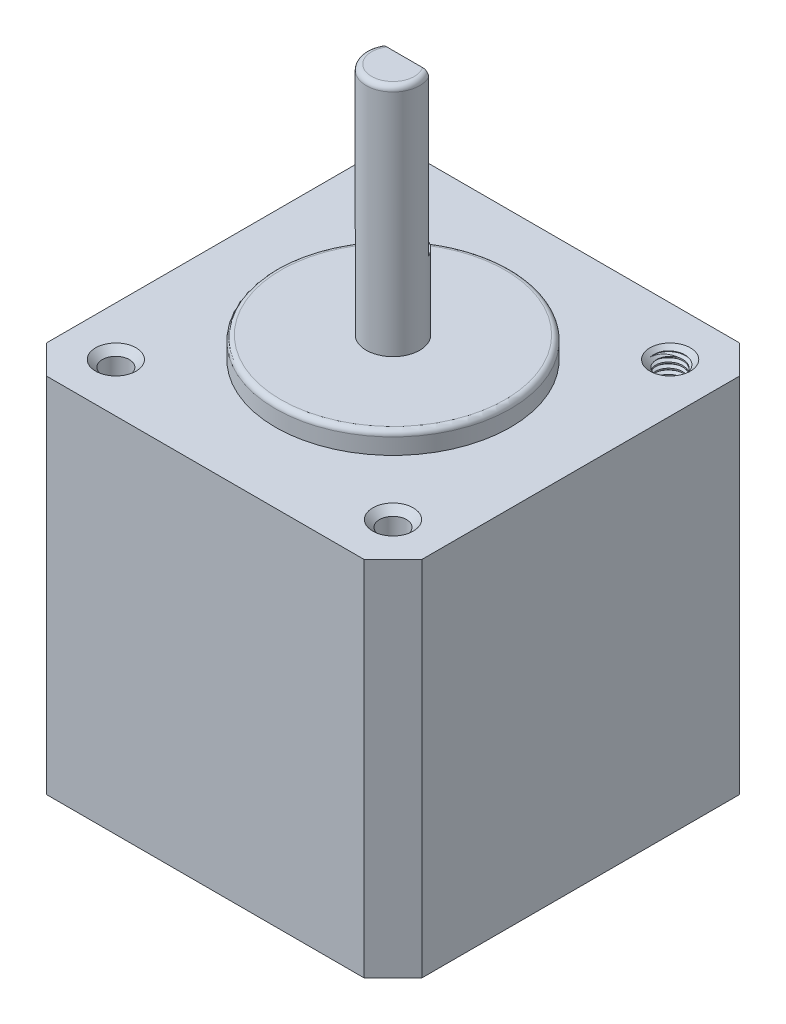
SolidWorks part; units mm, degrees
ref_plane "Front Plane" through (0, 0, 0) normal (0, 0, 1) x (1, 0, 0)
ref_plane "Top Plane" through (0, 0, 0) normal (0, 1, 0) x (1, 0, 0)
ref_plane "Right Plane" through (0, 0, 0) normal (1, 0, 0) x (0, 0, -1)
sketch "Sketch1" plane through (0, 0, 0) normal (0, 1, 0) x (1, 0, 0)
  line L1 (-17.6, -17.6) -> (17.6, -17.6)
  line L2 (-17.6, -17.6) -> (-17.6, 17.6)
  line L3 (-17.6, 17.6) -> (17.6, 17.6)
  line L4 (17.6, -17.6) -> (17.6, 17.6)
  line L5 (-17.6, -17.6) -> (17.6, 17.6) construction
  line L6 (-17.6, 17.6) -> (17.6, -17.6) construction
  point P0 (0, 0)
  dimension "D1" = 35.2
extrude "Boss-Extrude1" add sketch "Sketch1" along normal blind 34
hole_wizard "#39 (0.0995) Diameter Hole1" positions "Sketch2" profile "Sketch4" hole size "#39" standard "ANSI Inch"
sketch "Sketch2" plane through (0, 34, 0) normal (0, 1, 0) x (1, 0, 0)
  line L0 (-17.6, 17.6) -> (17.6, -17.6) construction
  line L3 (-13, -13) -> (13, -13) construction
  line L4 (-13, -13) -> (-13, 13) construction
  line L5 (-13, 13) -> (13, 13) construction
  line L6 (13, -13) -> (13, 13) construction
  line L7 (-13, -13) -> (13, 13) construction
  line L8 (-13, 13) -> (13, -13) construction
  line L9 (17.6, -17.6) -> (17.6, 17.6) construction
  point P8 (13, 13)
  point P63 (-13, -13)
  point P64 (-13, 13)
  point P65 (13, -13)
  dimension "D1" = 26
  dimension "D2" = 4.6
sketch "Sketch4" plane through (13, 34, 13) normal (1, 0, 0) x (0, 0, 1)
  line L0 (0, 0) -> (0, 5.2953)
  line L1 (0, 5.2953) -> (1.2636, 4.536)
  line L2 (1.2636, 4.536) -> (1.2636, 0.635)
  line L3 (1.2636, 0.635) -> (1.8986, 0)
  line L5 (1.8986, 0) -> (0, 0)
  line L6 (-1.2636, 0.635) -> (-1.8986, 0) construction
  line L10 (0, 5.2953) -> (-1.2637, 4.536) construction
  line L11 (0, -6.35) -> (0, 107.95) construction
  dimension "Hole Dia." = 2.5273
  dimension "Hole Depth" = 4.536
  dimension "Near C'Sink Dia." = 3.7973
  dimension "Near C'Sink Angle" = 90
  dimension "Drill Angle" = 118
thread "M3 threads" pitch 0.5 method cut profile "Thread Profile3" start angle 0, offset 0, length 4.5, pitch 0.5, diameter 2.5273
ref_plane "Plane3" through (-14.2636, 33.365, -13) normal (0, 0, 1) x (-1, 0, 0)
sketch "Thread Profile3" plane through (-14.2636, 33.365, -13) normal (0, 0, 1) x (-1, 0, 0)
  line L0 (0, 0) -> (0, 0.5) construction
  line L1 (0, 0) -> (0.2706, 0.1562)
  line L2 (0.2706, 0.1562) -> (0.2706, 0.2187)
  line L3 (0.2706, 0.2187) -> (0, 0.375)
  line L4 (0.2706, 0.1875) -> (0, 0.1875) construction
  line L11 (0, 0) -> (0, 0.375)
  point P2 (0, 0)
  dimension "Pitch" = 0.5
  dimension "Profile_Angle" = 60
  dimension "Profile_Land" = 0.0625
  dimension "Profile_Height" = 0.2706
sketch "Sketch7" plane through (0, 34, 0) normal (0, 1, 0) x (1, 0, 0)
  line L0 (17.6, 17.6) -> (-17.6, -17.6) construction
  circle A0 centre (0, 0) radius 11.025
  dimension "D1" = 22.05
extrude "collar" add sketch "Sketch7" along normal blind 2
sketch "Sketch8" plane through (0, 36, 0) normal (0, 1, 0) x (1, 0, 0)
  circle A0 centre (0, 0) radius 2.506
  dimension "D1" = 5.012
extrude "drive" add sketch "Sketch8" along normal blind 22
sketch "Sketch9" plane through (0, 58, 0) normal (0, 1, 0) x (1, 0, 0)
  line L0 (2.25, 1.1034) -> (-2.25, 1.1034)
  circle A0 centre (0, 0) radius 2.506 construction
  arc A1 (2.25, 1.1034) -> (-2.25, 1.1034) centre (0, 0) ccw
  dimension "D1" = 4.5
extrude "drive slot" cut sketch "Sketch9" against normal blind 15
fillet "Fillet1" radius 0.5 2 edges at (0, 58, 2.506) (0, 36, 11.025)
sketch "Sketch11" plane through (0, 34, 0) normal (0, 1, 0) x (1, 0, 0)
  line L0 (-17.6, -17.6) -> (17.6, -17.6) construction
  line L1 (-17.6, -14.8986) -> (-17.6, -17.6)
  line L2 (-14.8986, 14.8986) -> (-14.8986, -14.8986) construction
  line L4 (14.8986, 14.8986) -> (14.8986, -14.8987) construction
  line L7 (17.6, -17.6) -> (17.6, 17.6) construction
  line L8 (-14.8986, 14.8986) -> (14.8986, 14.8986) construction
  line L9 (-14.8986, -17.6) -> (-17.6, -17.6)
  line L10 (-14.8986, -14.8986) -> (14.8986, -14.8987) construction
  line L11 (-14.8986, 17.6) -> (-17.6, 17.6)
  line L14 (17.6, 14.8986) -> (14.8986, 17.6)
  line L15 (17.6, -14.8987) -> (14.8986, -17.6)
  line L16 (-14.8986, 17.6) -> (-17.6, 14.8986)
  line L17 (-17.6, -14.8986) -> (-14.8986, -17.6)
  line L18 (17.6, -14.8987) -> (17.6, -17.6)
  line L19 (17.6, 17.6) -> (14.8986, 17.6)
  line L20 (17.6, 17.6) -> (17.6, 14.8986)
  line L21 (17.6, -17.6) -> (14.8986, -17.6)
  line L22 (-17.6, 17.6) -> (-17.6, 14.8986)
  circle A0 centre (13, 13) radius 1.8986 construction
  point P0 (0, 0)
  point P8 (0, 0)
extrude "body corners" cut sketch "Sketch11" against normal through all
thread "Thread1" pitch 0.5 method cut profile "Thread Profile4" start angle 0, offset 0.254, length 0, pitch 0.5, diameter 2.5273
ref_plane "Plane4" through (14.2636, 29.21, -13) normal (0, 0, 1) x (1, 0, 0)
sketch "Thread Profile4" plane through (14.2636, 29.21, -13) normal (0, 0, 1) x (1, 0, 0)
  line L0 (0, 0) -> (0, 0.5) construction
  line L1 (0, 0) -> (0.2706, 0.1562)
  line L2 (0.2706, 0.1562) -> (0.2706, 0.2187)
  line L3 (0.2706, 0.2187) -> (0, 0.375)
  line L4 (0.2706, 0.1875) -> (0, 0.1875) construction
  line L11 (0, 0) -> (0, 0.375)
  point P2 (0, 0)
  dimension "Pitch" = 0.5
  dimension "Profile_Angle" = 60
  dimension "Profile_Land" = 0.0625
  dimension "Profile_Height" = 0.2706
